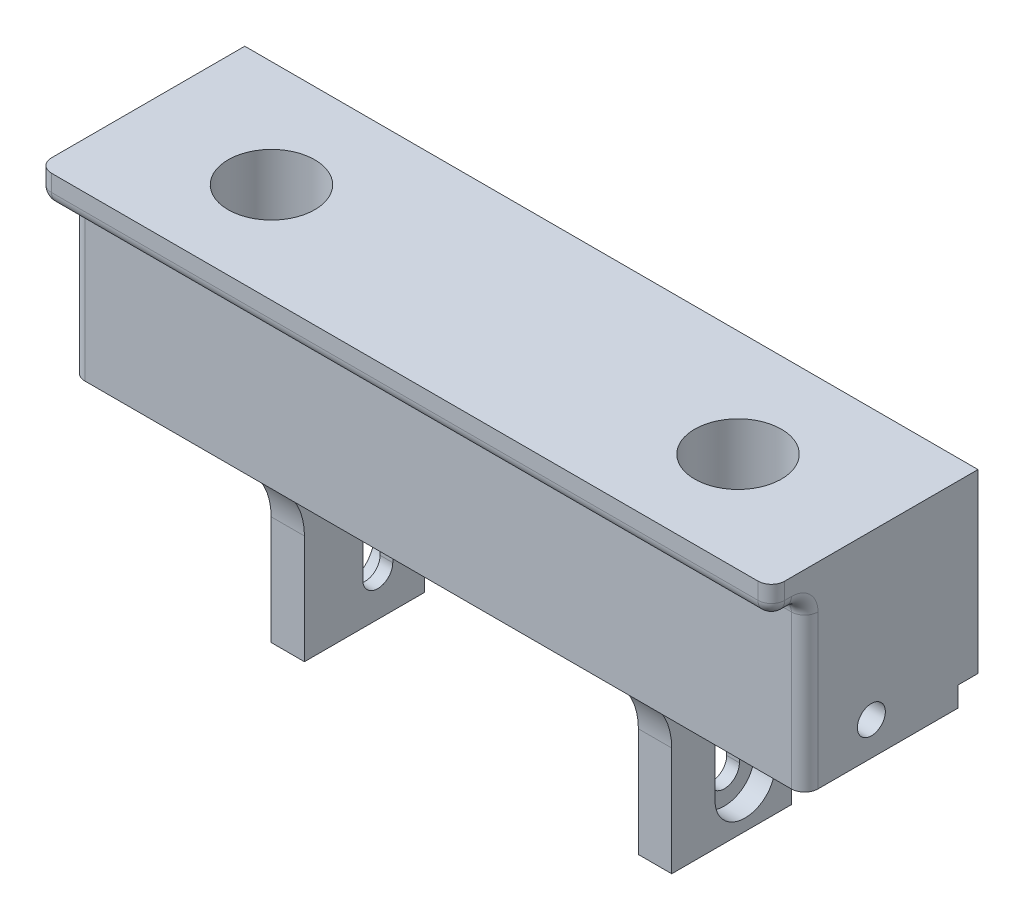
SolidWorks part; units mm, degrees
ref_plane "Ebene vorne" through (0, 0, 0) normal (0, 0, 1) x (1, 0, 0)
ref_plane "Ebene oben" through (0, 0, 0) normal (0, 1, 0) x (1, 0, 0)
ref_plane "Ebene rechts" through (0, 0, 0) normal (1, 0, 0) x (0, 0, -1)
sketch "Skizze2" plane through (0, 0, 0) normal (0, 0, 1) x (1, 0, 0)
  line L0 (-25.05, -25) -> (-25.05, 0)
  line L1 (-25.05, 0) -> (25.05, 0)
  line L2 (25.05, 0) -> (25.05, -25)
  line L3 (25.05, -25) -> (30.05, -25)
  line L4 (30.05, -25) -> (30.05, 0)
  line L6 (-30.05, 0) -> (-30.05, -25)
  line L7 (-30.05, -25) -> (-25.05, -25)
  line L9 (30.05, 0) -> (55, 0)
  line L10 (55, 0) -> (55, 29.5)
  line L11 (-30.05, 0) -> (-55, 0)
  line L12 (-55, 0) -> (-55, 29.5)
  line L13 (55, 29.5) -> (-55, 29.5)
  dimension "D1" = 110
  dimension "D2" = 5
  dimension "D3" = 29.5
  dimension "D4" = 25
  dimension "D5" = 50.1
extrude "Aufsatz-Linear austragen2" add sketch "Skizze2" along normal mid plane 26 contours L6 L7 L0 L1 L2 L3 L4 region at (0, 12.8008, 0)
hole_wizard "Stirnsenkung Langloch für M4 Flachkopfschraube mit Schlitz12" positions "Skizze3" profile "Skizze4" size "M4" standard "DIN" slot yes end condition up to next
sketch "Skizze3" plane through (30.05, 0, 0) normal (1, 0, 0) x (0, 0, -1)
  line L0 (6, -3) -> (6, -21) construction
  line L1 (13, 0) -> (13, -25) construction
  point P0 (6, -12)
  dimension "D1" = 18
  dimension "D2" = 12
  dimension "D3" = 7
sketch "Skizze4" plane through (30.05, -12, -6) normal (0, 1, 0) x (0, 0, -1)
  line L0 (0, 0) -> (0, 5)
  line L1 (0, 5) -> (2.25, 5)
  line L3 (2.25, 5) -> (2.25, 3.1)
  line L4 (2.25, 3.1) -> (4.5, 3.1)
  line L5 (4.5, 3.1) -> (4.5, 0)
  line L7 (4.5, 0) -> (0, 0)
  line L11 (0, -6.35) -> (0, 107.95) construction
  dimension "Bohrerdurchmesser" = 4.5
  dimension "Bohrungstiefe" = 5
  dimension "Senkdurchmesser2" = 9
  dimension "Senktiefe2" = 3.1
sketch "Skizze5" plane through (30.05, 0, 0) normal (1, 0, 0) x (0, 0, -1)
  line L0 (-10, 0) -> (-10, 25)
  line L1 (-13, -25) -> (-5, -25)
  line L2 (-13, -25) -> (-13, 25)
  line L3 (-10, 0) -> (-5, 0)
  line L4 (-5, -25) -> (-5, 0)
  line L5 (-10, 25) -> (-13, 25)
  line L6 (-13, 0) -> (-13, 29.5) construction
  dimension "D1" = 8
  dimension "D2" = 25
  dimension "D3" = 3
  dimension "D4" = 50
extrude "Schnitt-Linear austragen1" cut sketch "Skizze5" against normal through all and the other way through all
fillet "Verrundung1" radius 10 2 edges at (-27.55, 0, 5) (27.55, 0, 5)
sketch "Skizze9" plane through (0, 0, 0) normal (1, 0, 0) x (0, 0, -1)
  line L0 (13, 29.5) -> (16, 29.5)
  line L1 (-10, 0) -> (13, 0) construction
  line L4 (16, 3) -> (13, 3)
  line L5 (13, 0) -> (13, 29.5) construction
  line L7 (13, 29.5) -> (13, 3)
  line L9 (16, 29.5) -> (16, 3)
  dimension "D1" = 3
  dimension "D4" = 3
extrude "Aufsatz-Linear austragen4" add sketch "Skizze9" along normal up to surface and the other way up to surface up to face at (55, 18.1667, 3.3333) other way up to face at (-55, 18.1667, 3.3333)
sketch "Skizze18" plane through (0, 0, 13) normal (0, 0, 1) x (1, 0, 0)
  line L1 (-55, 29.5) -> (55, 29.5)
  line L2 (-55, 29.5) -> (-55, 25)
  line L3 (-55, 25) -> (55, 25)
  line L4 (55, 29.5) -> (55, 25)
  line L5 (0, 25) -> (0, 29.5) construction
  line L6 (-55, 27.25) -> (55, 27.25) construction
  point P140 (0, 27.25)
extrude "Aufsatz-Linear austragen5" add sketch "Skizze18" along normal blind 2
hole_wizard "Ø4.2 (4.2) Durchmesser Bohrung1" positions "Skizze12" profile "Skizze13" hole size "Ø4.2" standard "DIN" end condition through all
sketch "Skizze12" plane through (55, 0, 0) normal (1, 0, 0) x (0, 0, -1)
  line L0 (-10, 0) -> (13, 0) construction
  point P0 (0, 5)
  dimension "D1" = 5
  dimension "D2" = 0
sketch "Skizze13" plane through (55, 5, 0) normal (0, 1, 0) x (0, 0, -1)
  line L0 (0, 0) -> (0, 110)
  line L1 (0, 110) -> (2.1, 110)
  line L2 (2.1, 110) -> (2.1, 0)
  line L5 (2.1, 0) -> (0, 0)
  line L11 (0, -6.35) -> (0, 107.95) construction
  dimension "Bohrerdurchmesser" = 4.2
  dimension "Bohrungstiefe" = 110
mirror "Spiegeln2" about plane through (0, 0, 0) normal (1, 0, 0) of "Stirnsenkung Langloch für M4 Flachkopfschraube mit Schlitz12"
sketch "Skizze19" plane through (0, 29.5, 0) normal (0, 1, 0) x (1, 0, 0)
  line L0 (0, 0) -> (0, 10.71) construction
  circle A0 centre (-35, 0) radius 6.5
  circle A1 centre (35, 0) radius 6.5
  dimension "D2" = 13
  dimension "D1" = 35
extrude "Schnitt-Linear austragen2" cut sketch "Skizze19" against normal blind 11
hole_wizard "M5 Gewindebohrung1" positions "Skizze20" profile "Skizze22" tap size "M5" standard "DIN" end condition up to next
sketch "Skizze20" plane through (0, 18.5, 0) normal (0, 1, 0) x (1, 0, 0)
  line L0 (0, 16.6404) -> (0, -8.1318) construction
  point P0 (-35, 0)
  dimension "D1" = 35
sketch "Skizze22" plane through (-35, 18.5, 0) normal (1, 0, 0) x (0, 0, 1)
  line L0 (0, 0) -> (0, 11.4)
  line L1 (0, 11.4) -> (2.1, 11.4)
  line L2 (2.1, 11.4) -> (2.1, 0)
  line L5 (2.1, 0) -> (0, 0)
  line L11 (0, -6.35) -> (0, 107.95) construction
  dimension "Bohrerdurchmesser" = 4.2
  dimension "Bohrungstiefe" = 11.4
cosmetic thread "Bohrungsgewinde1" parameters "D2"=5
fillet "Verrundung2" radius 2 8 edges at (0, 25, 15) (55, 27.25, 15) (-55, 27.25, 15) (55, 12.5, 10) (55, 25, 12.5) (-55, 12.5, 10) (-55, 25, 12.5) (0, 25, 10)
mirror "Spiegeln3" about plane through (0, 0, 0) normal (1, 0, 0) of "M5 Gewindebohrung1"
